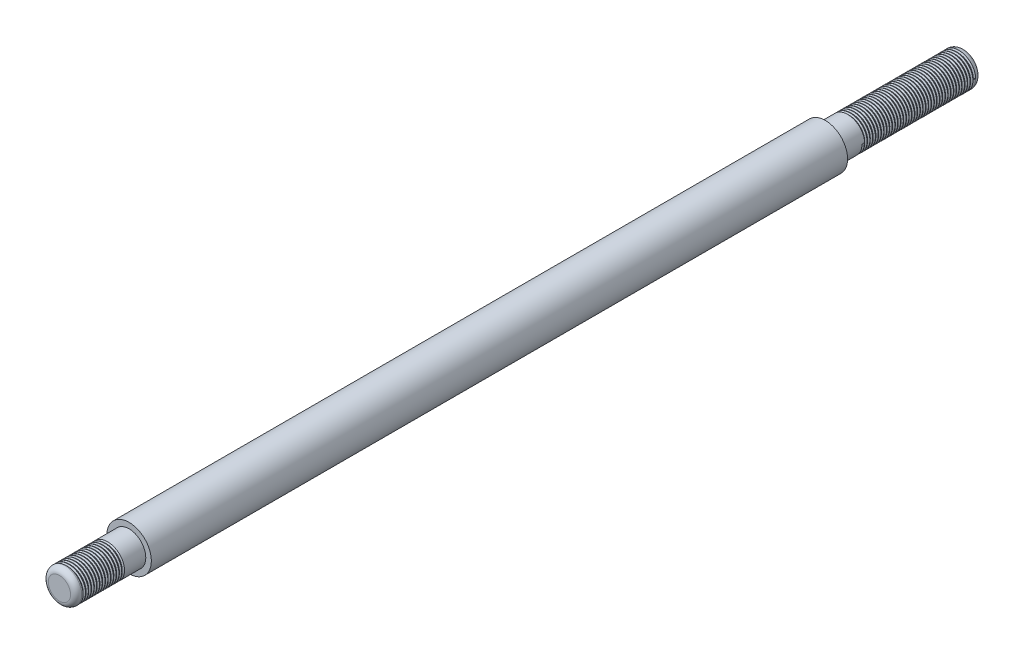
SolidWorks part; units mm, degrees
material "1023 碳钢板 (SS)"
ref_plane "前视基准面" through (0, 0, 0) normal (0, 0, 1) x (1, 0, 0)
ref_plane "上视基准面" through (0, 0, 0) normal (0, 1, 0) x (1, 0, 0)
ref_plane "右视基准面" through (0, 0, 0) normal (1, 0, 0) x (0, 0, -1)
sketch "草图1" plane through (0, 0, 0) normal (0, 0, 1) x (1, 0, 0)
  circle A0 centre (0, 0) radius 8
extrude "凸台-拉伸1" add sketch "草图1" along normal blind 250
sketch "草图2" plane through (0, 0, 250) normal (0, 0, 1) x (1, 0, 0)
  circle A0 centre (0, 0) radius 6
extrude "凸台-拉伸2" add sketch "草图2" along normal blind 25
sketch "草图3" plane through (0, 0, 0) normal (0, 0, -1) x (-1, 0, 0)
  circle A0 centre (0, 0) radius 6
extrude "凸台-拉伸3" add sketch "草图3" along normal blind 50
fillet "圆角1" radius 2 1 edges at (-6, 0, -50)
fillet "圆角2" radius 2 1 edges at (6, 0, 275)
thread "螺纹线1" pitch 1 method cut profile "螺纹线轮廓1" start angle 0, offset 0, length 40, pitch 1, diameter 12
ref_plane "基准面1" through (6, 0, -48) normal (0, -1, 0) x (1, 0, 0)
sketch "螺纹线轮廓1" plane through (6, 0, -48) normal (0, -1, 0) x (1, 0, 0)
  line L0 (0, 0) -> (0, 1) construction
  line L11 (0, 0) -> (0, 0.875)
  line L12 (0, 0.875) -> (-0.5413, 0.5625)
  line L13 (-0.5413, 0.5625) -> (-0.5413, 0.3125)
  line L15 (-0.5413, 0.3125) -> (0, 0)
  line L17 (-0.5413, 0.4375) -> (0, 0.4375) construction
  point P2 (0, 0)
  dimension "Pitch" = 1
  dimension "Profile_Angle" = 60
  dimension "Profile_Land" = 0.25
  dimension "Profile_Height" = 0.5413
thread "螺纹线2" pitch 1 method cut profile "螺纹线轮廓2" start angle 0, offset 0, length 15, pitch 1, diameter 12
ref_plane "基准面2" through (-6, 0, 273) normal (0, -1, 0) x (-1, 0, 0)
sketch "螺纹线轮廓2" plane through (-6, 0, 273) normal (0, -1, 0) x (-1, 0, 0)
  line L0 (0, 0) -> (0, 1) construction
  line L11 (0, 0) -> (0, 0.875)
  line L12 (0, 0.875) -> (-0.5413, 0.5625)
  line L13 (-0.5413, 0.5625) -> (-0.5413, 0.3125)
  line L15 (-0.5413, 0.3125) -> (0, 0)
  line L17 (-0.5413, 0.4375) -> (0, 0.4375) construction
  point P2 (0, 0)
  dimension "Pitch" = 1
  dimension "Profile_Angle" = 60
  dimension "Profile_Land" = 0.25
  dimension "Profile_Height" = 0.5413
